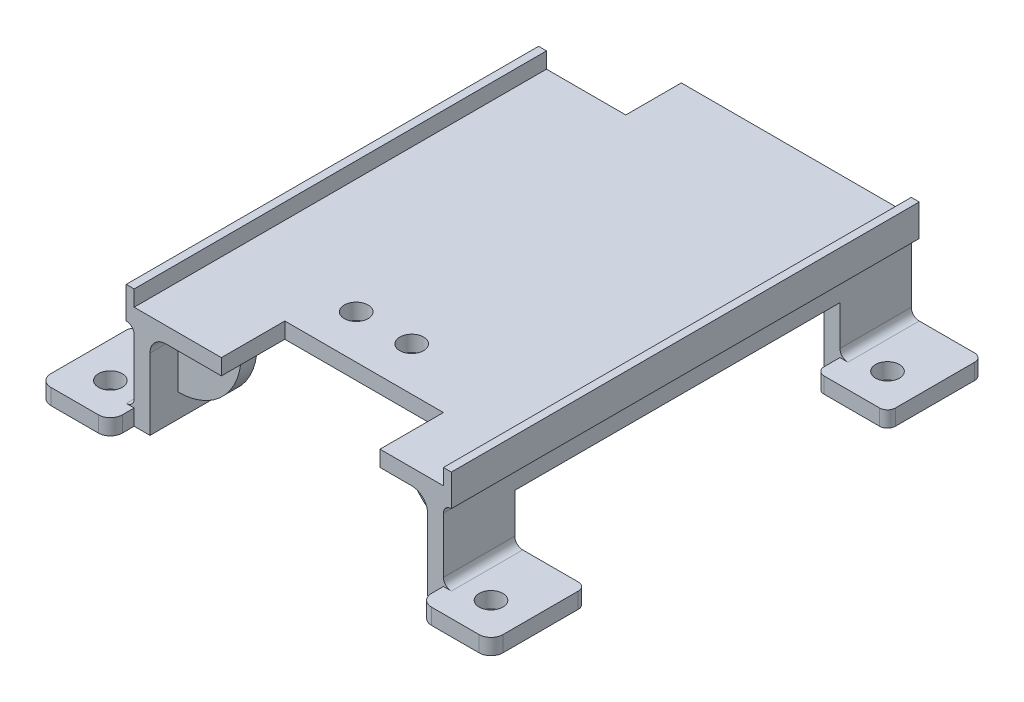
SolidWorks part; units mm, degrees
ref_plane "Front Plane" through (0, 0, 0) normal (0, 0, 1) x (1, 0, 0)
ref_plane "Top Plane" through (0, 0, 0) normal (0, 1, 0) x (1, 0, 0)
ref_plane "Right Plane" through (0, 0, 0) normal (1, 0, 0) x (0, 0, -1)
sketch "Sketch1" plane through (0, 0, 0) normal (0, 1, 0) x (1, 0, 0)
  line L1 (0, 0) -> (57, 0)
  line L2 (0, 0) -> (0, 59)
  line L3 (0, 59) -> (57, 59)
  line L4 (57, 0) -> (57, 59)
  dimension "D1" = 57
  dimension "D2" = 59
extrude "Boss-Extrude1" add sketch "Sketch1" along normal blind 13
sketch "Sketch2" plane through (57, 0, 0) normal (1, 0, 0) x (0, 0, -1)
  line L0 (0, 13) -> (59, 13) construction
  line L1 (9, 13) -> (50, 13)
  line L2 (9, 13) -> (9, 0)
  line L3 (9, 0) -> (50, 0)
  line L4 (50, 13) -> (50, 0)
  line L5 (0, 0) -> (59, 0) construction
  line L6 (0, 13) -> (0, 0) construction
  dimension "D1" = 9
  dimension "D2" = 9
extrude "Cut-Extrude1" cut sketch "Sketch2" against normal blind 9
sketch "Sketch4" plane through (0, 13, 0) normal (0, 1, 0) x (1, 0, 0)
  line L0 (0, 59) -> (0, 0) construction
  line L1 (0, 52) -> (10, 52)
  line L2 (0, 52) -> (0, 59)
  line L3 (0, 59) -> (10, 59)
  line L4 (10, 52) -> (10, 59)
  line L5 (57, 59) -> (0, 59) construction
  dimension "D1" = 10
  dimension "D2" = 7
extrude "Cut-Extrude3" cut sketch "Sketch4" against normal through all
sketch "Sketch5" plane through (0, 0, 0) normal (-1, 0, 0) x (0, 0, 1)
  line L0 (-52, 13) -> (0, 13) construction
  line L1 (-43, 13) -> (-9, 13)
  line L2 (-43, 13) -> (-43, 0)
  line L3 (-43, 0) -> (-9, 0)
  line L4 (-9, 13) -> (-9, 0)
  line L5 (-52, 0) -> (0, 0) construction
  line L6 (-52, 0) -> (-52, 13) construction
  line L7 (0, 13) -> (0, 0) construction
  dimension "D1" = 9
  dimension "D2" = 9
extrude "Cut-Extrude4" cut sketch "Sketch5" against normal blind 9
sketch "Sketch6" plane through (0, 13, 0) normal (0, 1, 0) x (1, 0, 0)
  line L0 (0, 0) -> (57, 0) construction
  line L1 (9, 0) -> (48, 0)
  line L2 (9, 0) -> (9, 59)
  line L3 (9, 59) -> (48, 59)
  line L4 (48, 0) -> (48, 59)
  line L5 (57, 59) -> (10, 59) construction
sketch "Sketch7" plane through (0, 0, 0) normal (0, 0, 1) x (1, 0, 0)
  line L0 (0, 0) -> (57, 0) construction
  line L1 (9, 13) -> (48, 13)
  line L2 (9, 13) -> (9, 0)
  line L3 (9, 0) -> (48, 0)
  line L4 (48, 13) -> (48, 0)
sketch "Sketch8" plane through (0, 0, 0) normal (0, 0, 1) x (1, 0, 0)
  line L0 (9, 13) -> (48, 13) construction
  line L1 (20, 13) -> (40, 13)
  line L2 (20, 13) -> (20, 0)
  line L3 (20, 0) -> (40, 0)
  line L4 (40, 13) -> (40, 0)
  line L5 (9, 0) -> (48, 0) construction
  line L6 (9, 13) -> (9, 0) construction
  point P8 (20, 6.5)
  dimension "D1" = 11
  dimension "D2" = 20
extrude "Cut-Extrude5" cut sketch "Sketch8" against normal blind 8
sketch "Sketch9" plane through (0, 0, 0) normal (0, -1, 0) x (-1, 0, 0)
  line L0 (-57, 59) -> (-10, 59) construction
  line L1 (-11, 0) -> (-46, 0)
  line L2 (-11, 0) -> (-11, 59)
  line L3 (-11, 59) -> (-46, 59)
  line L4 (-46, 0) -> (-46, 59)
  dimension "D1" = 35
  dimension "D2" = 2
extrude "Cut-Extrude6" cut sketch "Sketch9" against normal blind 11
sketch "Sketch10" plane through (0, 13, 0) normal (0, 1, 0) x (1, 0, 0)
  line L1 (10, 52) -> (19, 52)
  line L2 (10, 52) -> (10, 59)
  line L3 (10, 59) -> (19, 59)
  line L4 (19, 52) -> (19, 59)
  dimension "D1" = 9
extrude "Cut-Extrude7" cut sketch "Sketch10" against normal through all
sketch "Sketch11" plane through (0, 13, 0) normal (0, 1, 0) x (1, 0, 0)
  line L1 (48, 0) -> (57, 0)
  line L2 (48, 0) -> (48, 9)
  line L3 (48, 9) -> (57, 9)
  line L4 (57, 0) -> (57, 9)
extrude "Cut-Extrude8" cut sketch "Sketch11" against normal blind 11
sketch "Sketch12" plane through (0, 13, 0) normal (0, 1, 0) x (1, 0, 0)
  line L1 (48, 59) -> (57, 59)
  line L2 (48, 59) -> (48, 50)
  line L3 (48, 50) -> (57, 50)
  line L4 (57, 59) -> (57, 50)
extrude "Cut-Extrude9" cut sketch "Sketch12" against normal blind 11
sketch "Sketch13" plane through (0, 13, 0) normal (0, 1, 0) x (1, 0, 0)
  line L1 (0, 52) -> (9, 52)
  line L2 (0, 52) -> (0, 43)
  line L3 (0, 43) -> (9, 43)
  line L4 (9, 52) -> (9, 43)
extrude "Cut-Extrude10" cut sketch "Sketch13" against normal blind 11
sketch "Sketch14" plane through (0, 13, 0) normal (0, 1, 0) x (1, 0, 0)
  line L1 (9, 0) -> (0, 0)
  line L2 (9, 0) -> (9, 9)
  line L3 (9, 9) -> (0, 9)
  line L4 (0, 0) -> (0, 9)
extrude "Cut-Extrude11" cut sketch "Sketch14" against normal blind 11
sketch "Sketch15" plane through (0, 0, 0) normal (0, -1, 0) x (-1, 0, 0)
  line L0 (-46, 59) -> (-46, 0) construction
  line L1 (-48, 9) -> (-46, 9)
  line L2 (-48, 9) -> (-48, 50)
  line L3 (-48, 50) -> (-46, 50)
  line L4 (-46, 9) -> (-46, 50)
extrude "Cut-Extrude12" cut sketch "Sketch15" against normal blind 8
sketch "Sketch16" plane through (0, 0, 0) normal (0, -1, 0) x (-1, 0, 0)
  line L0 (-11, 0) -> (-11, 52) construction
  line L1 (-9, 9) -> (-11, 9)
  line L2 (-9, 9) -> (-9, 43)
  line L3 (-9, 43) -> (-11, 43)
  line L4 (-11, 9) -> (-11, 43)
extrude "Cut-Extrude13" cut sketch "Sketch16" against normal blind 8
sketch "Sketch31" plane through (11, 0, 0) normal (1, 0, 0) x (0, 0, -1)
  line L0 (0, 11) -> (52, 11) construction
  line L1 (3.5, 11) -> (5.5, 11)
  line L2 (3.5, 11) -> (3.5, 3)
  line L3 (3.5, 3) -> (5.5, 3)
  line L4 (5.5, 11) -> (5.5, 3)
  line L6 (0, 11) -> (0, 0) construction
  line L7 (9, 8) -> (9, 0) construction
  line L8 (0, 0) -> (9, 0) construction
  point P10 (0, 5.5)
  dimension "D1" = 3.5
  dimension "D2" = 3.5
  dimension "D3" = 3
revolve "Revolve3" add sketch "Sketch31" angle 90 about L1 reverse direction yes
sketch "Sketch32" plane through (11, 0, 0) normal (1, 0, 0) x (0, 0, -1)
  line L0 (5.5, 11) -> (52, 11) construction
  line L1 (46.5, 11) -> (48.5, 11)
  line L2 (46.5, 11) -> (46.5, 3)
  line L3 (46.5, 3) -> (48.5, 3)
  line L4 (48.5, 11) -> (48.5, 3)
  line L6 (43, 8) -> (43, 0) construction
  line L7 (52, 0) -> (52, 11) construction
  line L8 (43, 0) -> (52, 0) construction
  dimension "D1" = 3.5
  dimension "D2" = 3.5
  dimension "D3" = 3
revolve "Revolve4" add sketch "Sketch32" angle 90 about L1 reverse direction yes
sketch "Sketch33" plane through (0, 11, 0) normal (0, -1, 0) x (1, 0, 0)
  line L0 (40, 0) -> (40, -8) construction
  line L1 (40, -3.5) -> (46, -3.5)
  line L2 (40, -3.5) -> (40, -5.5)
  line L3 (40, -5.5) -> (46, -5.5)
  line L4 (46, -3.5) -> (46, -5.5)
  line L5 (46, -59) -> (46, 0) construction
  line L6 (46, 0) -> (40, 0) construction
  dimension "D1" = 3.5
revolve "Revolve5" add sketch "Sketch33" angle 90 about L4 reverse direction yes
sketch "Sketch34" plane through (46, 0, 0) normal (-1, 0, 0) x (0, 0, 1)
  line L1 (-53.5, 3) -> (-55.5, 3)
  line L2 (-53.5, 3) -> (-53.5, 11)
  line L3 (-53.5, 11) -> (-55.5, 11)
  line L4 (-55.5, 3) -> (-55.5, 11)
  line L5 (-59, 11) -> (-5.5, 11) construction
  line L6 (-50, 8) -> (-50, 0) construction
  line L7 (-59, 11) -> (-59, 0) construction
  line L8 (-59, 0) -> (-50, 0) construction
  point P10 (-55.5, 7)
  dimension "D1" = 3.5
  dimension "D2" = 3.5
  dimension "D3" = 3
revolve "Revolve6" add sketch "Sketch34" angle 90 about L3
sketch "Sketch42" plane through (0, 13, 0) normal (0, 1, 0) x (1, 0, 0)
  line L0 (9, 0) -> (9, 52) construction
  line L1 (48, 59) -> (48, 0) construction
  line L2 (48, 59) -> (19, 59) construction
  circle A0 centre (23.5, 13.5) radius 1.5
  circle A1 centre (30.5, 13.5) radius 1.5
  dimension "D5" = 3
  dimension "D6" = 3
  dimension "D1" = 14.5
  dimension "D2" = 17.5
  dimension "D3" = 45.5
  dimension "D4" = 45.5
extrude "Cut-Extrude15" cut sketch "Sketch42" against normal through all
sketch "Sketch46" plane through (48, 0, 0) normal (1, 0, 0) x (0, 0, -1)
  line L0 (59, 2) -> (59, 13) construction
  line L1 (0, 13) -> (59, 13)
  line L2 (0, 13) -> (0, 11)
  line L3 (0, 11) -> (59, 11)
  line L4 (59, 13) -> (59, 11)
  dimension "D1" = 2
extrude "Boss-Extrude3" add sketch "Sketch46" along normal blind 1
sketch "Sketch47" plane through (0, 13, 0) normal (0, 1, 0) x (1, 0, 0)
  line L0 (40, 0) -> (49, 0) construction
  line L1 (49, 59) -> (48, 59)
  line L2 (49, 59) -> (49, 0)
  line L3 (49, 0) -> (48, 0)
  line L4 (48, 59) -> (48, 0)
  dimension "D1" = 1
extrude "Boss-Extrude4" add sketch "Sketch47" along normal blind 2
sketch "Sketch48" plane through (9, 0, 0) normal (-1, 0, 0) x (0, 0, 1)
  line L1 (-52, 13) -> (0, 13)
  line L2 (-52, 13) -> (-52, 11)
  line L3 (-52, 11) -> (0, 11)
  line L4 (0, 13) -> (0, 11)
  dimension "D1" = 2
extrude "Boss-Extrude5" add sketch "Sketch48" along normal blind 1
sketch "Sketch49" plane through (0, 13, 0) normal (0, 1, 0) x (1, 0, 0)
  line L0 (8, 0) -> (20, 0) construction
  line L1 (8, 52) -> (9, 52)
  line L2 (8, 52) -> (8, 0)
  line L3 (8, 0) -> (9, 0)
  line L4 (9, 52) -> (9, 0)
  dimension "D1" = 1
extrude "Boss-Extrude6" add sketch "Sketch49" along normal blind 2
sketch "Sketch50" plane through (0, 0, 0) normal (0, 0, 1) x (1, 0, 0)
  line L0 (0, 0) -> (11, 0) construction
  line L1 (0, 2) -> (9, 2)
  line L2 (0, 2) -> (0, 0)
  line L3 (0, 0) -> (9, 0)
  line L4 (9, 2) -> (9, 0)
  line L6 (48, 2) -> (57, 2)
  line L7 (48, 2) -> (48, 0)
  line L8 (48, 0) -> (57, 0)
  line L9 (57, 2) -> (57, 0)
extrude "Boss-Extrude7" add sketch "Sketch50" along normal blind 3
sketch "Sketch51" plane through (0, 0, -43) normal (0, 0, 1) x (1, 0, 0)
  line L1 (9, 2) -> (0, 2)
  line L2 (9, 2) -> (9, 0)
  line L3 (9, 0) -> (0, 0)
  line L4 (0, 2) -> (0, 0)
extrude "Boss-Extrude8" add sketch "Sketch51" along normal blind 3
sketch "Sketch52" plane through (0, 0, -50) normal (0, 0, 1) x (1, 0, 0)
  line L1 (48, 2) -> (57, 2)
  line L2 (48, 2) -> (48, 0)
  line L3 (48, 0) -> (57, 0)
  line L4 (57, 2) -> (57, 0)
extrude "Boss-Extrude9" add sketch "Sketch52" along normal blind 3
sketch "Sketch53" plane through (0, 2, 0) normal (0, 1, 0) x (1, 0, 0)
  line L0 (9, 52) -> (0, 52) construction
  line L1 (0, 52) -> (0, 40) construction
  line L2 (57, 59) -> (48, 59) construction
  line L3 (57, 47) -> (57, 59) construction
  line L4 (9, 9) -> (0, 9) construction
  line L5 (0, 9) -> (0, -3) construction
  line L6 (57, 9) -> (48, 9) construction
  line L7 (57, -3) -> (57, 9) construction
  circle A0 centre (4.5, 44.5) radius 1.5
  circle A1 centre (52.5, 51.5) radius 1.5
  circle A2 centre (52.5, 1.5) radius 1.5
  circle A3 centre (4.5, 1.5) radius 1.5
  dimension "D1" = 3
  dimension "D4" = 3
  dimension "D7" = 3
  dimension "D10" = 3
  dimension "D2" = 7.5
  dimension "D3" = 4.5
  dimension "D5" = 7.5
  dimension "D6" = 4.5
  dimension "D8" = 7.5
  dimension "D9" = 4.5
  dimension "D11" = 7.5
  dimension "D12" = 4.5
extrude "Cut-Extrude16" cut sketch "Sketch53" against normal through all
fillet "Fillet2" radius 1.5 4 edges at (57, 1, 3) (48, 1, 3) (9, 1, 3) (0, 1, 3)
fillet "Fillet3" radius 1 2 edges at (48, 11, -29.5) (9, 11, -26)
fillet "Fillet6" radius 1 8 edges at (0, 1, -9) (57, 1, -9) (48, 1, -47) (57, 1, -47) (57, 1, -59) (0, 1, -52) (0, 1, -40) (9, 1, -40) first distance on face at (0, 1, -3.75) first distance on face at (57, 1, -3.75) first distance on face at (48, 1, -48.5) first distance on face at (57, 1, -53) first distance on face at (0, 1, -46) first distance on face at (9, 1, -41.5)
fillet "Fillet7" radius 1 4 edges at (9, 2, -47.5) (9, 2, -4.5) (48, 2, -4.5) (48, 2, -54.5) first distance on face at (9, 5.5, -26) first distance on face at (48, 5.5, -29.5)
fillet "Fillet8" radius 2 6 edges at (11, 11, -50.25) (46, 11, -57.25) (11, 11, -1.75) (46, 11, -1.75) (11, 11, -26) (46, 11, -29.5) first distance on face at (11, 5.875, -26) first distance on face at (46, 6.125, -29.5)
